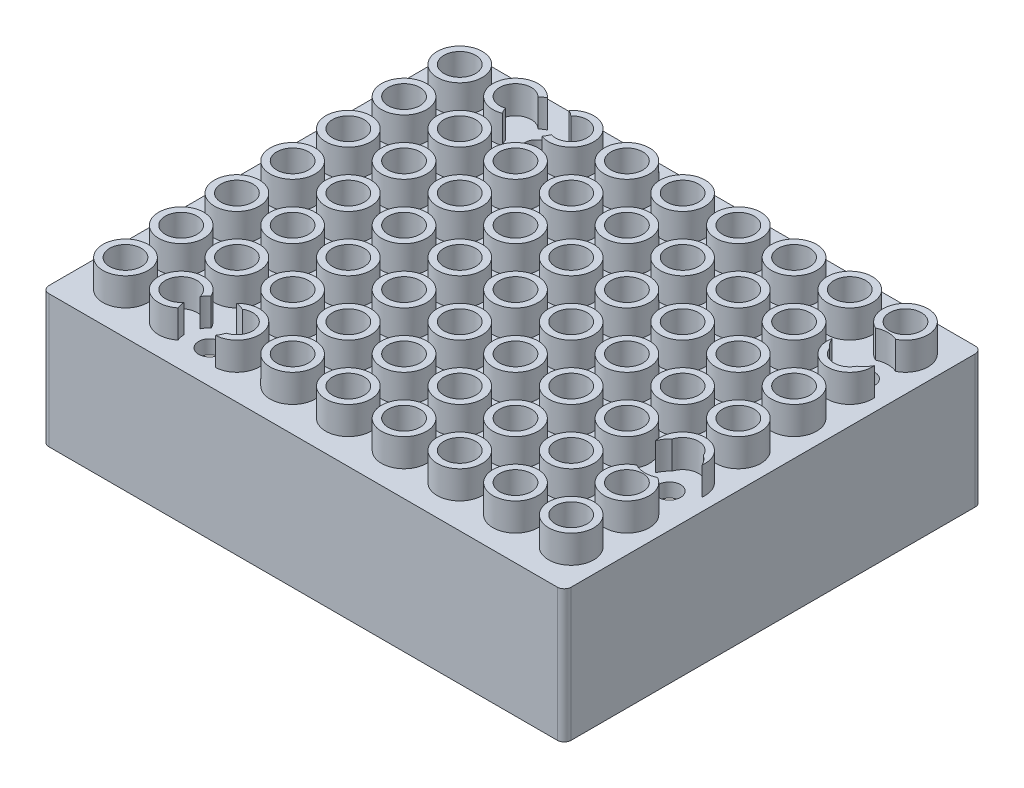
SolidWorks part; units mm, degrees
ref_plane "Front Plane" through (0, 0, 0) normal (0, 0, 1) x (1, 0, 0)
ref_plane "Top Plane" through (0, 0, 0) normal (0, 1, 0) x (1, 0, 0)
ref_plane "Right Plane" through (0, 0, 0) normal (1, 0, 0) x (0, 0, -1)
sketch "Sketch1" plane through (0, 0, 0) normal (0, 1, 0) x (1, 0, 0)
  line L1 (-37.5, -30) -> (37.5, -30)
  line L2 (-37.5, -30) -> (-37.5, 30)
  line L3 (-37.5, 30) -> (37.5, 30)
  line L4 (37.5, -30) -> (37.5, 30)
  line L5 (-37.5, -30) -> (37.5, 30) construction
  line L6 (-37.5, 30) -> (37.5, -30) construction
  point P0 (0, 0)
  dimension "D1" = 75
  dimension "D2" = 60
extrude "Boss-Extrude1" add sketch "Sketch1" along normal blind 19.05
fillet "Fillet1" radius 1 4 edges at (-37.5, 9.525, 30) (-37.5, 9.525, -30) (37.5, 9.525, -30) (37.5, 9.525, 30)
sketch "Sketch3" plane through (0, 19.05, 0) normal (0, 1, 0) x (1, 0, 0)
  line L0 (-37.5, -18.85) -> (-34, -18.85)
  line L1 (-37.5, 29) -> (-37.5, -29) construction
  line L2 (-34, -18.85) -> (-34, -28.25)
  line L3 (-34, -28.25) -> (33.125, -28.25)
  line L4 (33.125, -28.25) -> (33.125, -15.25)
  line L5 (33.125, -15.25) -> (36, -12.375)
  line L6 (36, -12.375) -> (36, 20.375)
  line L7 (36, 20.375) -> (33.125, 23.25)
  line L8 (33.125, 23.25) -> (33.125, 26.75)
  line L9 (33.125, 26.75) -> (-34, 26.75)
  line L10 (-34, 26.75) -> (-34, -6)
  line L11 (-34, -6) -> (-37.5, -6)
  line L12 (-37.5, -6) -> (-37.5, -18.85)
  line L13 (-36.5, -30) -> (36.5, -30) construction
  dimension "D1" = 55
  dimension "D2" = 70
  dimension "D3" = 32.75
  dimension "D4" = 3.5
  dimension "D5" = 13
  dimension "D6" = 225
  dimension "D7" = 32.75
  dimension "D8" = 9.4
  dimension "D9" = 1.75
  dimension "D10" = 3.5
extrude "Arduino Cavity" cut sketch "Sketch3" against normal blind 19.125 from offset 2 offset against normal yes
sketch "Sketch4" plane through (-37.5, 0, 0) normal (-1, 0, 0) x (0, 0, 1)
  circle A0 centre (-17.925, 6.4) radius 5.5
  arc A1 (-21.925, 6.4) -> (-13.925, 6.4) centre (-17.925, 6.4) ccw construction
  dimension "D1" = 11
extrude "9V Barrel Plug hole" cut sketch "Sketch4" against normal blind 19.125
sketch "Sketch5" plane through (0, 19.05, 0) normal (0, 1, 0) x (1, 0, 0)
  line L0 (-37.5, 29) -> (-37.5, -29) construction
  line L1 (-36.5, -30) -> (36.5, -30) construction
  circle A0 centre (-31.5, -24) radius 3.2375
  dimension "D1" = 6.475
  dimension "D2" = 6
  dimension "D3" = 6
extrude "Bump 1" add sketch "Sketch5" along normal blind 4
sketch "Sketch6" plane through (0, 23.05, 0) normal (0, 1, 0) x (1, 0, 0)
  circle A0 centre (-31.5, -24) radius 2.275
  circle A1 centre (-31.5, -24) radius 3.2375 construction
  dimension "D1" = 4.55
extrude "Cut-Extrude3" cut sketch "Sketch6" against normal up to surface (4 mm away) up to face at (-31.5, 19.05, 20.7625)
pattern_linear "LPattern1" count 7 spacing 8 along (0, 0, -1) of "Bump 1", "Cut-Extrude3"
pattern_linear "LPattern2" count 9 spacing 8 along (1, 0, 0) of "LPattern1"
sketch "Sketch2" plane through (0, 0, 0) normal (0, -1, 0) x (-1, 0, 0)
  line L0 (-36.5, 30) -> (36.5, 30) construction
  line L2 (37.5, 30) -> (37.5, -30) construction
  circle A0 centre (18.2, -25.2) radius 1.6
  circle A1 centre (19.5, 23) radius 1.6
  circle A2 centre (-32.6, -10) radius 1.6
  circle A3 centre (-32.6, 17.9) radius 1.6
  dimension "D1" = 3.2
  dimension "D2" = 3.2
  dimension "D3" = 3.2
  dimension "D4" = 3.2
  dimension "D5" = 50.8
  dimension "D6" = 15.2
  dimension "D7" = 1.3
  dimension "D8" = 27.9
  dimension "D9" = 5.1
  dimension "D10" = 7
  dimension "D11" = 18
extrude "Mount Holes" cut sketch "Sketch2" against normal through all both and the other way through all
sketch "Sketch7" plane through (0, 19.05, 0) normal (0, 1, 0) x (1, 0, 0)
  circle A0 centre (32.6, -10) radius 3.5
  circle A1 centre (32.6, 17.9) radius 3.5
  circle A2 centre (-18.2, -25.2) radius 3.5
  circle A3 centre (-19.5, 23) radius 3.5
  arc A4 (31.383, -11.0387) -> (33.9145, -10.9121) centre (32.6, -10) ccw construction
  dimension "D1" = 7
  dimension "D2" = 7
  dimension "D3" = 7
  dimension "D4" = 7
extrude "Cut-Extrude4" cut sketch "Sketch7" along normal up to surface (4 mm away) up to face at (32.5, 23.05, 26.275)
equation "\"D2@Sketch2\"=\"D1@Sketch2\""
equation "\"D3@Sketch2\"=\"D1@Sketch2\""
equation "\"D4@Sketch2\"=\"D1@Sketch2\""
equation "\"D2@Sketch7\"=\"D1@Sketch7\""
equation "\"D3@Sketch7\"=\"D1@Sketch7\""
equation "\"D4@Sketch7\"=\"D1@Sketch7\""
